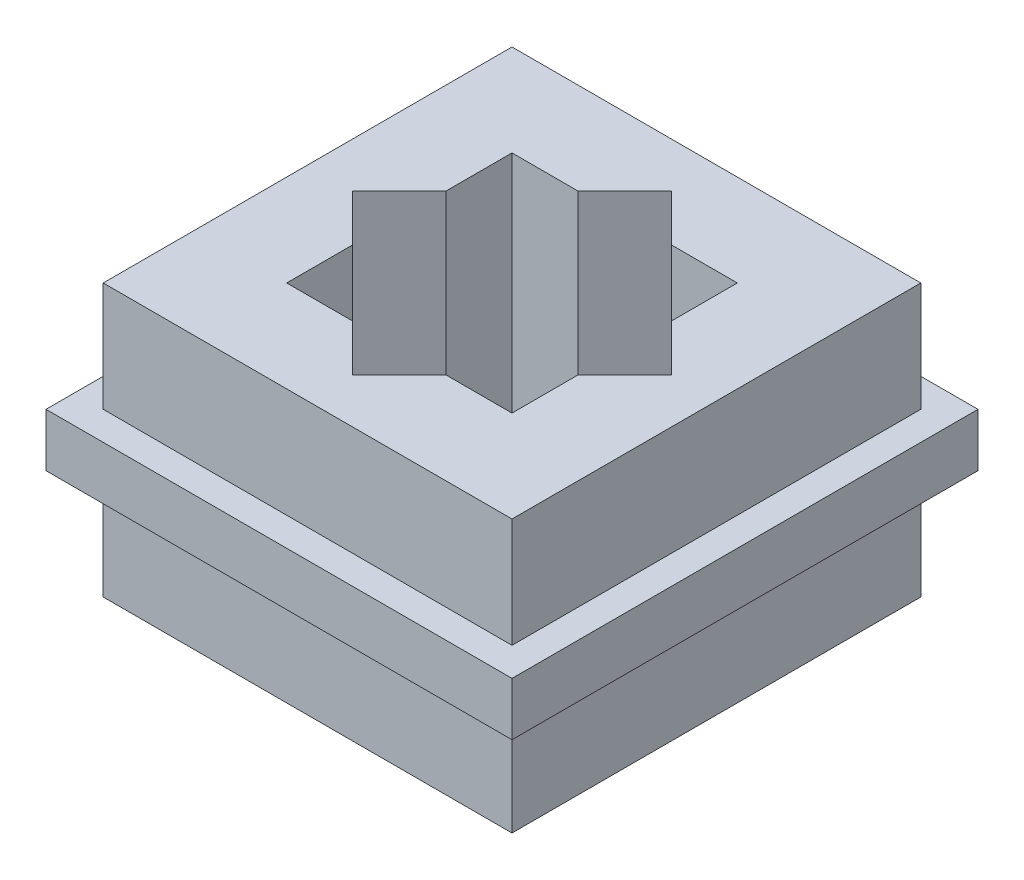
SolidWorks part; units mm, degrees
ref_plane "Front" through (0, 0, 0) normal (0, 0, 1) x (1, 0, 0)
ref_plane "Top" through (0, 0, 0) normal (0, 1, 0) x (1, 0, 0)
ref_plane "Right" through (0, 0, 0) normal (1, 0, 0) x (0, 0, -1)
sketch "Sketch1" plane through (0, 0, 0) normal (0, 1, 0) x (1, 0, 0)
  line L1 (-12.7, 12.7) -> (12.7, 12.7)
  line L2 (-12.7, 12.7) -> (-12.7, -12.7)
  line L3 (-12.7, -12.7) -> (12.7, -12.7)
  line L4 (12.7, 12.7) -> (12.7, -12.7)
  line L5 (-12.7, 12.7) -> (12.7, -12.7) construction
  line L6 (-12.7, -12.7) -> (12.7, 12.7) construction
  point P0 (0, 0)
  dimension "D1" = 25.4
extrude "Boss-Extrude1" add sketch "Sketch1" along normal mid plane 16.9
sketch "Sketch2" plane through (0, 0, 0) normal (0, 1, 0) x (1, 0, 0)
  line L1 (14.478, -14.478) -> (-14.478, -14.478)
  line L2 (14.478, -14.478) -> (14.478, 14.478)
  line L3 (14.478, 14.478) -> (-14.478, 14.478)
  line L4 (-14.478, -14.478) -> (-14.478, 14.478)
  line L5 (14.478, -14.478) -> (-14.478, 14.478) construction
  line L6 (14.478, 14.478) -> (-14.478, -14.478) construction
  point P0 (0, 0)
  dimension "D1" = 28.956
extrude "Boss-Extrude2" add sketch "Sketch2" along normal mid plane 3.302
sketch "Sketch3" plane through (0, 8.45, 0) normal (0, 1, 0) x (1, 0, 0)
  line L12 (-7, 5.7279) -> (-5.7279, 7)
  line L13 (-7, 7) -> (7, 7)
  line L14 (-7, 7) -> (-7, -7)
  line L15 (-7, -7) -> (7, -7)
  line L16 (7, 7) -> (7, -7)
  line L17 (-7, 7) -> (7, -7) construction
  line L18 (-7, -7) -> (7, 7) construction
  line L19 (-7, -5.7279) -> (-5.7279, -7)
  line L20 (5.7279, 7) -> (7, 5.7279)
  line L21 (5.7279, -7) -> (7, -5.7279)
  point P0 (0, 0)
  point P7 (0, 0)
  dimension "D1" = 14
  dimension "D2" = 18
extrude "Cut-Extrude1" cut sketch "Sketch3" against normal through all contours L15 L21 L16 L20 L13 L12 L14 L19 region at (0, 8.45, 0)
ref_axis "Axis1" through (0, 50, 0) along (0, -1, 0)
pattern_circular "CirPattern1" count 2 every 45 about axis through (0, 50, 0) along (0, -1, 0) of "Cut-Extrude1"
sketch "Sketch4" plane through (0, 8.45, 0) normal (0, 1, 0) x (1, 0, 0)
  line L0 (-7, -7) -> (-7, 7)
  line L1 (-7, -7) -> (7, -7)
  line L2 (-7, 7) -> (7, 7)
  line L3 (7, -7) -> (7, 7)
  line L4 (-7, -7) -> (7, 7) construction
  line L5 (-7, 7) -> (7, -7) construction
  line L6 (2.8995, 7) -> (5.7279, 7) construction
  line L7 (7, 5.7279) -> (7, 2.8995) construction
  line L8 (0, -9.8995) -> (-9.8995, 0)
  line L9 (0, -9.8995) -> (9.8995, 0)
  line L10 (-9.8995, 0) -> (0, 9.8995)
  line L11 (9.8995, 0) -> (0, 9.8995)
  line L12 (0, -9.8995) -> (0, 9.8995) construction
  line L13 (-9.8995, 0) -> (9.8995, 0) construction
  line L14 (-0.8995, 9) -> (-2.8995, 7) construction
  line L15 (0.8995, 9) -> (2.8995, 7) construction
  point P1 (0, 0)
  point P11 (0, 0)
extrude "Cut-Extrude2" cut sketch "Sketch4" against normal through all contours L11 L10 L8 L9 | L2 L3 L1 L0
